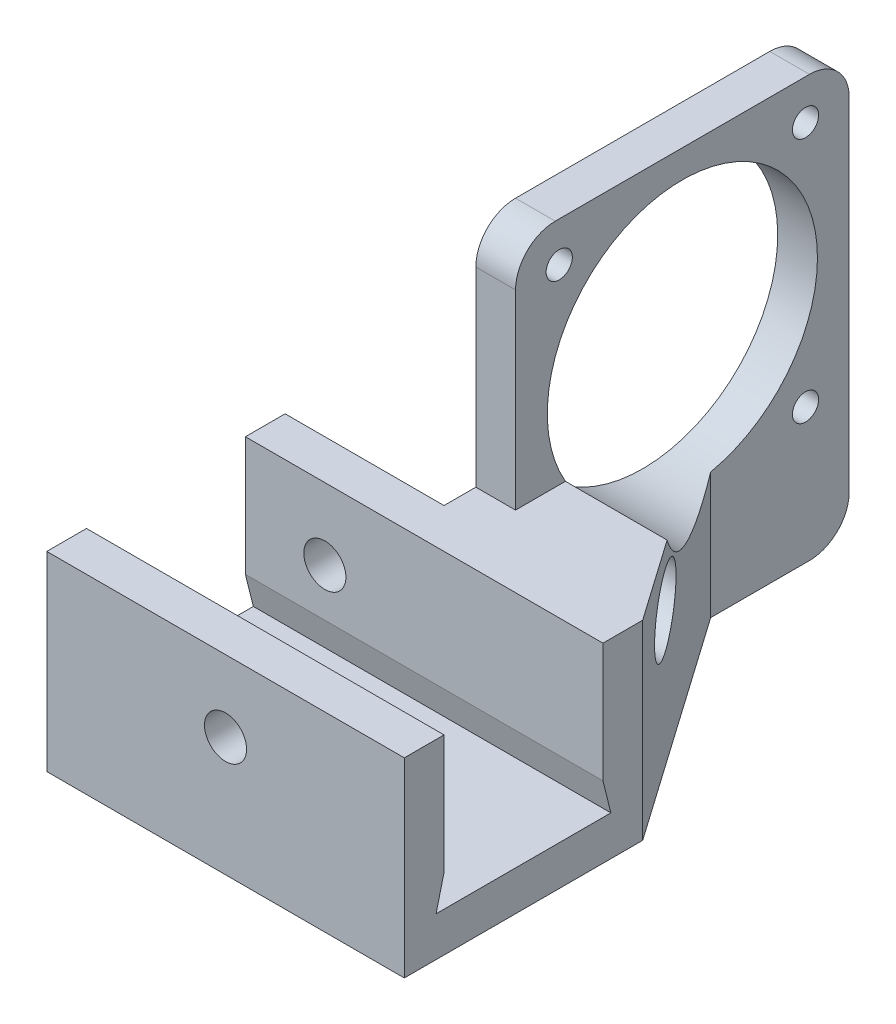
SolidWorks part; units mm, degrees
ref_plane "Front Plane" through (0, 0, 0) normal (0, 0, 1) x (1, 0, 0)
ref_plane "Top Plane" through (0, 0, 0) normal (0, 1, 0) x (1, 0, 0)
ref_plane "Right Plane" through (0, 0, 0) normal (1, 0, 0) x (0, 0, -1)
sketch "Sketch1" plane through (0, 0, 0) normal (0, 0, 1) x (1, 0, 0)
  line L1 (0, 0) -> (45, 0)
  line L2 (0, 0) -> (0, 24)
  line L3 (0, 24) -> (45, 24)
  line L4 (45, 0) -> (45, 24)
  dimension "D1" = 45
  dimension "D2" = 24
extrude "Boss-Extrude1" add sketch "Sketch1" along normal blind 5
sketch "Sketch2" plane through (0, 0, 0) normal (0, 0, -1) x (-1, 0, 0)
  line L1 (-25, 24) -> (-20, 24)
  line L2 (-25, 24) -> (-25, 0)
  line L3 (-25, 0) -> (-20, 0)
  line L4 (-20, 24) -> (-20, 0)
  line L5 (-45, 24) -> (0, 24) construction
  line L7 (0, 24) -> (0, 0) construction
  dimension "D1" = 5
  dimension "D2" = 20
extrude "Boss-Extrude2" add sketch "Sketch2" along normal blind 46
sketch "Sketch3" plane through (0, 0, 5) normal (0, 0, 1) x (1, 0, 0)
  line L0 (0, 24) -> (0, 0) construction
  line L1 (45, 0) -> (0, 0)
  line L2 (45, 0) -> (45, 5)
  line L3 (45, 5) -> (0, 5)
  line L4 (0, 0) -> (0, 5)
  dimension "D1" = 5
extrude "Boss-Extrude3" add sketch "Sketch3" along normal blind 20
chamfer "Chamfer2" distance 20 angle 55 1 edges at (25, 12, 0) first distance on face at (35, 12, 0)
chamfer "Chamfer3" distance 20 angle 55 1 edges at (20, 12, 0) first distance on face at (10, 12, 0)
sketch "Sketch4" plane through (0, 24, 0) normal (0, 1, 0) x (1, 0, 0)
  line L1 (20, 46) -> (25, 46)
  line L2 (20, 46) -> (20, 4)
  line L3 (20, 4) -> (25, 4)
  line L4 (25, 46) -> (25, 4)
  dimension "D1" = 42
  dimension "D2" = 5
extrude "Boss-Extrude4" add sketch "Sketch4" along normal blind 29
sketch "Sketch6" plane through (25, 0, 0) normal (1, 0, 0) x (0, 0, -1)
  line L0 (4, 53) -> (46, 53) construction
  line L2 (46, 53) -> (46, 0) construction
  circle A0 centre (25, 32.5) radius 17
  dimension "D1" = 34
  dimension "D2" = 20.5
  dimension "D3" = 21
extrude "Cut-Extrude1" cut sketch "Sketch6" against normal through all both and the other way through all
sketch "Sketch7" plane through (20, 0, 0) normal (-1, 0, 0) x (0, 0, 1)
  line L1 (-46, 53) -> (0, 53)
  line L2 (-46, 53) -> (-46, 9)
  line L3 (-46, 9) -> (0, 9)
  line L4 (0, 53) -> (0, 9)
  line L5 (5, 24) -> (5, 5) construction
  dimension "D1" = 44
  dimension "D2" = 5
extrude "Cut-Extrude2" cut sketch "Sketch7" along normal through all
sketch "Sketch8" plane through (20, 0, 0) normal (-1, 0, 0) x (0, 0, 1)
  line L1 (-40.5, 17) -> (-9.5, 17) construction
  line L2 (-40.5, 17) -> (-40.5, 48) construction
  line L3 (-40.5, 48) -> (-9.5, 48) construction
  line L4 (-9.5, 17) -> (-9.5, 48) construction
  line L5 (-40.5, 17) -> (-9.5, 48) construction
  line L6 (-40.5, 48) -> (-9.5, 17) construction
  circle A0 centre (-40.5, 48) radius 1.65
  circle A1 centre (-9.5, 48) radius 1.65
  circle A2 centre (-9.5, 17) radius 1.65
  circle A3 centre (-40.5, 17) radius 1.65
  point P0 (-25, 32.5)
  dimension "D3" = 3.3
  dimension "D1" = 31
  dimension "D2" = 31
extrude "Cut-Extrude3" cut sketch "Sketch8" against normal through all
sketch "Sketch9" plane through (25, 0, 0) normal (1, 0, 0) x (0, 0, -1)
  circle A0 centre (9.5, 17) radius 4.5
  dimension "D1" = 9
extrude "Cut-Extrude4" cut sketch "Sketch9" along normal through all
fillet "Fillet1" radius 5 3 edges at (22.5, 0, -46) (22.5, 53, -4) (22.5, 53, -46)
sketch "Sketch10" plane through (0, 0, 0) normal (0, -1, 0) x (1, 0, 0)
  line L0 (0, 25) -> (45, 25) construction
  line L1 (45, 25) -> (45, 0) construction
  circle A0 centre (22.5, 15) radius 2.65
  dimension "D2" = 5.3
  dimension "D1" = 10
  dimension "D3" = 22.5
extrude "Cut-Extrude5" cut sketch "Sketch10" against normal blind 10
sketch "Sketch11" plane through (0, 0, 5) normal (0, 0, 1) x (1, 0, 0)
  line L0 (45, 5) -> (0, 5) construction
  line L1 (0, 24) -> (0, 5) construction
  circle A0 centre (10, 15) radius 2.65
  dimension "D2" = 5.3
  dimension "D1" = 10
  dimension "D3" = 10
extrude "Cut-Extrude6" cut sketch "Sketch11" against normal blind 10
sketch "Sketch12" plane through (0, 0, 0) normal (0, 1, 0) x (1, 0, 0)
  line L1 (45, -25) -> (0, -25)
  line L2 (45, -25) -> (45, -30)
  line L3 (45, -30) -> (0, -30)
  line L4 (0, -25) -> (0, -30)
  dimension "D1" = 5
extrude "Boss-Extrude5" add sketch "Sketch12" along normal blind 24
sketch "Sketch13" plane through (0, 0, 30) normal (0, 0, 1) x (1, 0, 0)
  line L1 (45, 24) -> (45, 0) construction
  line L2 (0, 0) -> (45, 0) construction
  circle A0 centre (22.5, 15) radius 2.65
  dimension "D1" = 5.3
  dimension "D2" = 15
  dimension "D3" = 22.5
extrude "Cut-Extrude7" cut sketch "Sketch13" against normal blind 10
sketch "Sketch14" plane through (45, 0, 0) normal (1, 0, 0) x (0, 0, -1)
  line L0 (-25, 5) -> (-26, 5)
  line L1 (-26, 5) -> (-25, 9)
  line L2 (-25, 24) -> (-25, 5) construction
  line L3 (-25, 9) -> (-25, 5)
  line L4 (-5, 5) -> (-4, 5)
  line L5 (-4, 5) -> (-5, 9)
  line L6 (-5, 5) -> (-5, 24) construction
  line L7 (-5, 9) -> (-5, 5)
  dimension "D1" = 1
  dimension "D5" = 4
  dimension "D6" = 1
  dimension "D7" = 4
extrude "Cut-Extrude8" cut sketch "Sketch14" against normal through all both and the other way through all
